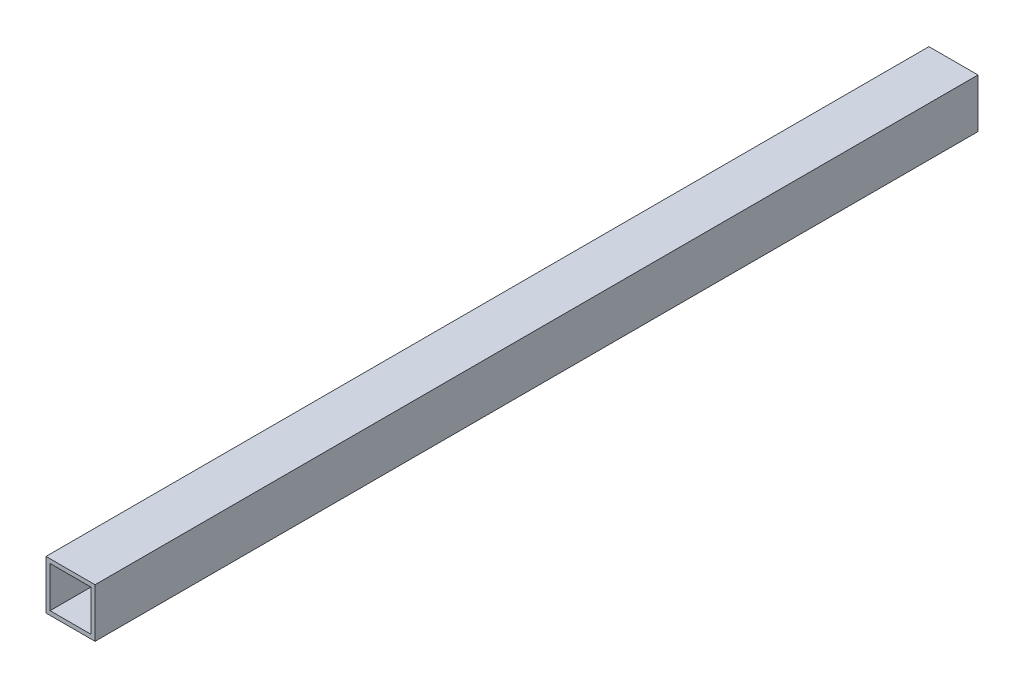
SolidWorks part; units mm, degrees
material "6061 Alloy"
ref_plane "Front Plane" through (0, 0, 0) normal (0, 0, 1) x (1, 0, 0)
ref_plane "Top Plane" through (0, 0, 0) normal (0, 1, 0) x (1, 0, 0)
ref_plane "Right Plane" through (0, 0, 0) normal (1, 0, 0) x (0, 0, -1)
sketch "Sketch1" plane through (0, 0, 0) normal (0, 0, 1) x (1, 0, 0)
  line L1 (-7.9375, -7.9375) -> (7.9375, -7.9375)
  line L2 (-7.9375, -7.9375) -> (-7.9375, 7.9375)
  line L3 (-7.9375, 7.9375) -> (7.9375, 7.9375)
  line L4 (7.9375, -7.9375) -> (7.9375, 7.9375)
  line L5 (-7.9375, -7.9375) -> (7.9375, 7.9375) construction
  line L6 (-7.9375, 7.9375) -> (7.9375, -7.9375) construction
  line L7 (-9.525, -9.525) -> (9.525, -9.525)
  line L8 (-9.525, -9.525) -> (-9.525, 9.525)
  line L9 (-9.525, 9.525) -> (9.525, 9.525)
  line L10 (9.525, -9.525) -> (9.525, 9.525)
  line L11 (-9.525, -9.525) -> (9.525, 9.525) construction
  line L12 (-9.525, 9.525) -> (9.525, -9.525) construction
  point P0 (0, 0)
  point P6 (0, 0)
  dimension "D1" = 19.05
  dimension "D2" = 19.05
  dimension "D3" = 1.5875
  dimension "D4" = 1.5875
extrude "Boss-Extrude1" add sketch "Sketch1" along normal mid plane 342.9
